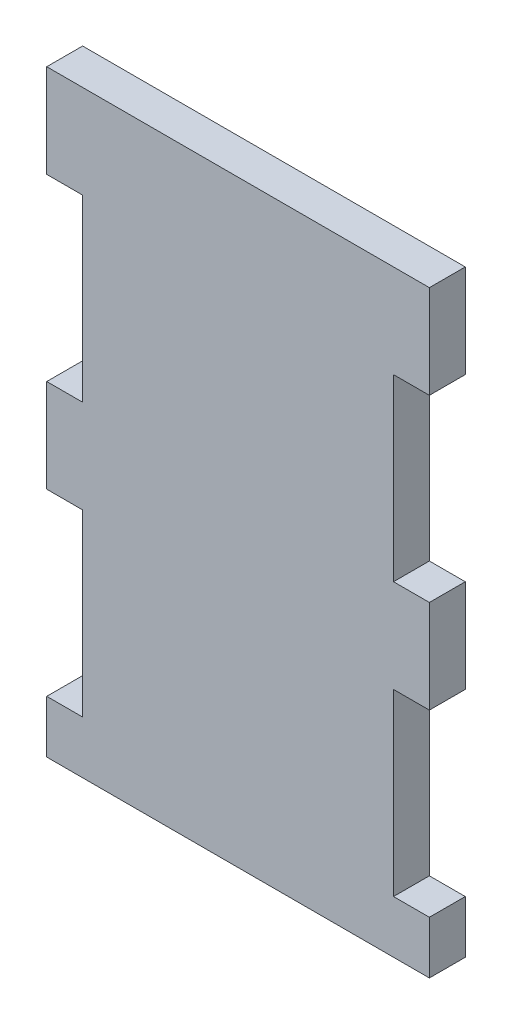
SolidWorks part; units mm, degrees
material "Oak"
ref_plane "Front Plane" through (0, 0, 0) normal (0, 0, 1) x (1, 0, 0)
ref_plane "Top Plane" through (0, 0, 0) normal (0, 1, 0) x (1, 0, 0)
ref_plane "Right Plane" through (0, 0, 0) normal (1, 0, 0) x (0, 0, -1)
sketch "Sketch1" plane through (0, 0, 0) normal (0, 0, 1) x (1, 0, 0)
  line L1 (-40.9935, 16.542) -> (-8.9935, 16.542)
  line L2 (-40.9935, 16.542) -> (-40.9935, -33.458)
  line L3 (-40.9935, -33.458) -> (-8.9935, -33.458)
  line L4 (-8.9935, 16.542) -> (-8.9935, -33.458)
  dimension "D1" = 50
  dimension "D2" = 32
extrude "Boss-Extrude1" add sketch "Sketch1" along normal blind 3
sketch "Sketch2" plane through (0, 0, 3) normal (0, 0, 1) x (1, 0, 0)
  line L0 (-40.9935, 16.542) -> (-40.9935, -33.458) construction
  line L1 (-40.9935, 8.742) -> (-37.9935, 8.742)
  line L2 (-40.9935, 8.742) -> (-40.9935, -6.258)
  line L3 (-40.9935, -6.258) -> (-37.9935, -6.258)
  line L4 (-37.9935, 8.742) -> (-37.9935, -6.258)
  line L5 (-8.9935, 16.542) -> (-40.9935, 16.542) construction
  line L6 (-8.9935, -33.458) -> (-8.9935, 16.542) construction
  line L7 (-8.9935, 8.742) -> (-11.9935, 8.742)
  line L8 (-8.9935, 8.742) -> (-8.9935, -6.258)
  line L9 (-8.9935, -6.258) -> (-11.9935, -6.258)
  line L10 (-11.9935, 8.742) -> (-11.9935, -6.258)
  point P8 (-39.4935, 8.742)
  dimension "D1" = 3
  dimension "D2" = 7.8
  dimension "D3" = 15
  dimension "D4" = 3
  dimension "D5" = 7.8
  dimension "D6" = 15
extrude "Cut-Extrude1" cut sketch "Sketch2" against normal through all
pattern_linear "LPattern1" count 3 spacing 22.8 along (0, -1, 0) of "Cut-Extrude1"
